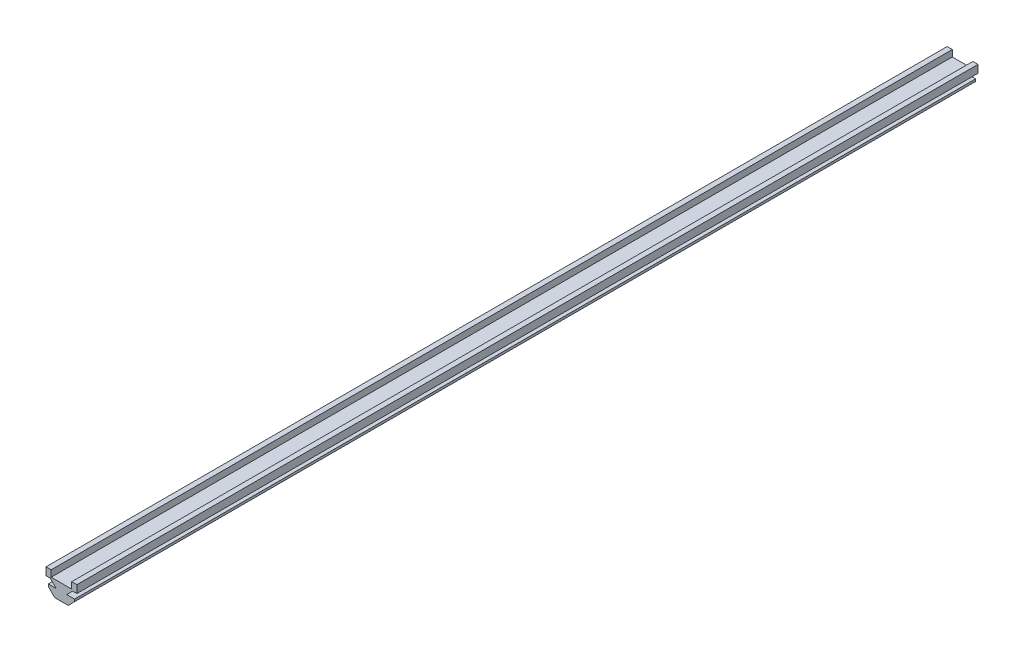
SolidWorks part; units mm, degrees
ref_plane "Alzado" through (0, 0, 0) normal (0, 0, 1) x (1, 0, 0)
ref_plane "Planta" through (0, 0, 0) normal (0, 1, 0) x (1, 0, 0)
ref_plane "Vista lateral" through (0, 0, 0) normal (1, 0, 0) x (0, 0, -1)
sketch "Croquis1" plane through (0, 0, 0) normal (0, 0, 1) x (1, 0, 0)
  line L0 (12.6279, -5.675) -> (15.1, -3.2029)
  line L8 (7.1649, -6.175) -> (10, -6.175)
  line L9 (15.1, -2.3) -> (15.1, -3.2029)
  line L10 (15.1, -2.3) -> (12.0429, -2.3)
  line L12 (7.3721, -5.675) -> (12.6279, -5.675)
  line L13 (10, -6.175) -> (10, 0.5) construction
  line L33 (7.3721, -5.675) -> (4.9, -3.2029)
  line L34 (4.9, -2.3) -> (4.9, -3.2029)
  line L35 (4.9, -2.3) -> (7.9571, -2.3)
  line L41 (12.0429, -2.3) -> (14.3429, 0)
  line L42 (7.9571, -2.3) -> (5.6571, 0)
  line L43 (14.3429, 0) -> (16, 0)
  line L49 (16, 0) -> (16, 3)
  line L50 (14, 3) -> (16, 3)
  line L51 (10, 0.5) -> (10, -6.175)
  line L54 (6, 0.5) -> (14, 0.5)
  line L56 (14, 0.5) -> (14, 3)
  line L62 (5.6571, 0) -> (4, 0)
  line L65 (7.1649, -6.175) -> (4.4, -3.4101)
  line L66 (4.4, -1.8) -> (4.4, -3.4101)
  line L67 (4.4, -1.8) -> (6.75, -1.8)
  line L68 (6.75, -1.8) -> (4.95, 0)
  line L69 (0, 0) -> (4.4, 0)
  line L70 (4.4, 0) -> (4.95, 0)
  line L75 (6, 0.5) -> (6, 3)
  line L76 (6, 3) -> (4, 3)
  line L77 (4, 0) -> (4, 3)
  line L89 (10, 0.5) -> (6, 0.5)
  point P3 (10, -5.675)
  dimension "D1" = 10
  dimension "D2" = 4
  dimension "D5" = 2
  dimension "D4" = 3
  dimension "D6" = 0.5
extrude "Saliente-Extruir1" add sketch "Croquis1" along normal blind 350 contours L77 L62 L42 L35 L34 L33 L12 L51 L54 L75 L76 | L56 L54 L51 L12 L0 L9 L10 L41 L43 L49 L50 region at (11.314, -5.5695, 0) region at (8.686, -5.5695, 0)
